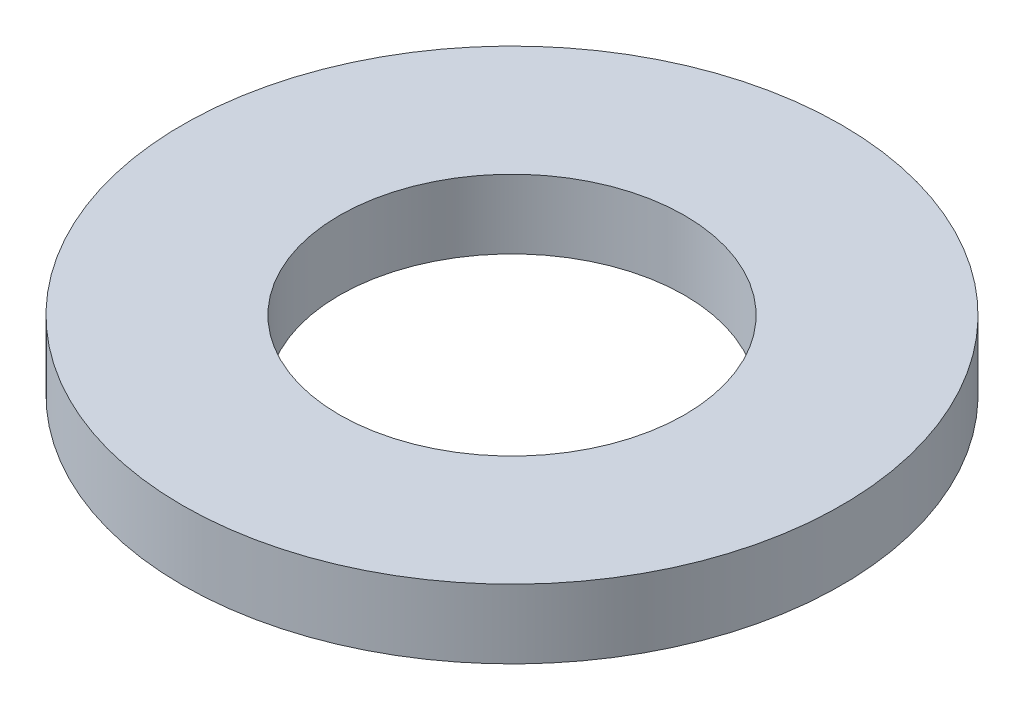
SolidWorks part; units mm, degrees
ref_plane "Front Plane" through (0, 0, 0) normal (0, 0, 1) x (1, 0, 0)
ref_plane "Top Plane" through (0, 0, 0) normal (0, 1, 0) x (1, 0, 0)
ref_plane "Right Plane" through (0, 0, 0) normal (1, 0, 0) x (0, 0, -1)
sketch "Sketch1" plane through (0, 0, 0) normal (0, 1, 0) x (1, 0, 0)
  circle A0 centre (0, 0) radius 52.5
  dimension "FLANGE_OD" = 105
extrude "Boss-Extrude1" add sketch "Sketch1" along normal blind 11
sketch "Sketch2" plane through (0, 0, 0) normal (0, 1, 0) x (1, 0, 0)
  circle A0 centre (0, 0) radius 27.5
  dimension "BORE_D" = 55
extrude "Cut-Extrude1" cut sketch "Sketch2" along normal through all
sketch "Sketch3" plane through (0, 11, 0) normal (0, 1, 0) x (1, 0, 0)
  circle A0 centre (0, 0) radius 19.3283 construction
  circle A1 centre (-19.3283, 0) radius 2.1395
  dimension "BOLT_D" = 4.2791
  dimension "BOLT_PCD" = 38.6566
extrude "Cut-Extrude2" cut sketch "Sketch3" against normal blind 9.5708 rebuild error yes
pattern_circular "CirPattern1" count 3 over 360 rebuild error yes
